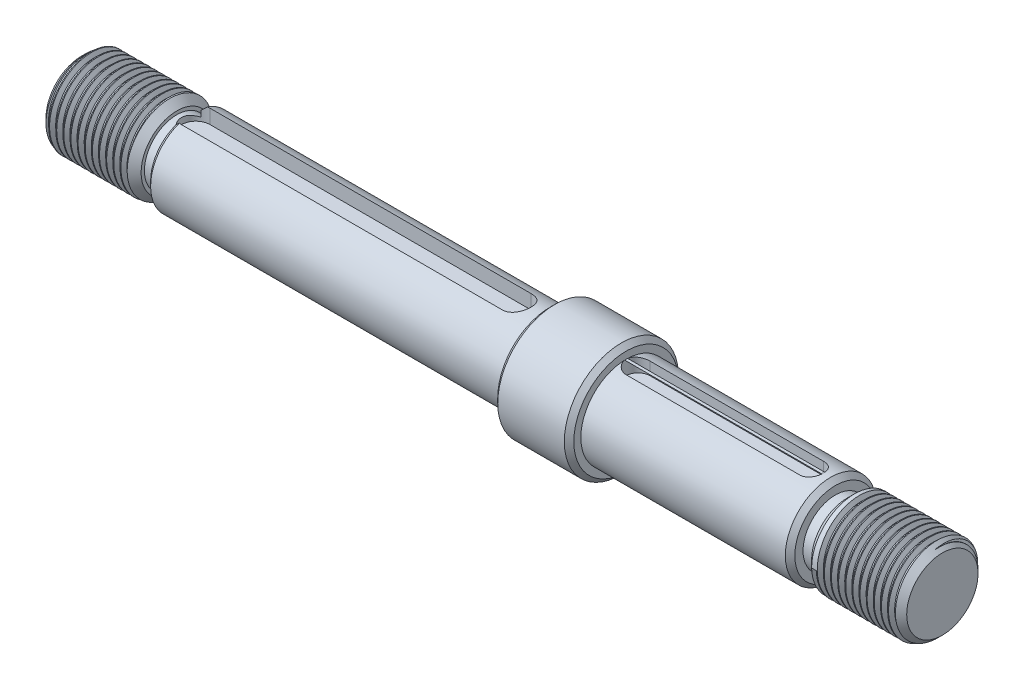
SolidWorks part; units mm, degrees
material "1.0503 (C45)"
ref_plane "前视基准面" through (0, 0, 0) normal (0, 0, 1) x (1, 0, 0)
ref_plane "上视基准面" through (0, 0, 0) normal (0, 1, 0) x (1, 0, 0)
ref_plane "右视基准面" through (0, 0, 0) normal (1, 0, 0) x (0, 0, -1)
sketch "轴轴向刨面" plane through (0, 0, 0) normal (0, 0, 1) x (1, 0, 0)
  line L0 (0, 0) -> (0, 7.5)
  line L3 (23.5, 9) -> (98.5, 9)
  line L4 (98.5, 9) -> (98.5, 11)
  line L5 (99.5, 12) -> (113.5, 12)
  line L6 (114.5, 11) -> (114.5, 9.525)
  line L7 (114.5, 9.525) -> (157.5, 9.525)
  line L8 (181, 7.5) -> (181, 0)
  line L10 (162.5, 9) -> (179.5, 9)
  line L12 (22.5, 6.8) -> (20, 6.8)
  line L13 (20, 6.8) -> (20, 7.5)
  line L14 (1.5, 9) -> (18.5, 9)
  line L16 (158.5, 8.525) -> (158.5, 6.8)
  line L17 (158.5, 6.8) -> (161, 6.8)
  line L18 (161, 6.8) -> (161, 7.5)
  line L19 (22.5, 8) -> (22.5, 6.8)
  line L20 (0, 0) -> (181, 0) construction
  line L21 (0, 0) -> (181, 0)
  line L22 (-25.1387, 0) -> (205.8562, 0) construction
  line L23 (0, 7.5) -> (1.5, 9)
  line L24 (20, 7.5) -> (18.5, 9)
  line L25 (23.5, 9) -> (22.5, 8)
  line L26 (157.5, 9.525) -> (158.5, 8.525)
  line L27 (161, 7.5) -> (162.5, 9)
  line L28 (179.5, 9) -> (181, 7.5)
  line L29 (98.5, 11) -> (99.5, 12)
  line L30 (113.5, 12) -> (114.5, 11)
  point P1 (0, 9)
  point P5 (22.5, 9)
  point P6 (98.5, 12)
  point P7 (158.5, 9.525)
  point P8 (114.5, 12)
  point P10 (161, 9)
  point P11 (181, 9)
  point P15 (20, 9)
  point P19 (0, 0)
  point P20 (0, 0)
  point P25 (0, 0)
  point P38 (0, 0)
  point P39 (161, 7.15)
  dimension "D2" = 20
  dimension "轮毂轴长" = 44
  dimension "40减速机长" = 76
  dimension "轴肩宽" = 16
  dimension "退刀槽宽" = 2.5
  dimension "大端螺纹长度" = 20
  dimension "减速机直径" = 18
  dimension "退刀槽小径" = 13.6
  dimension "轴肩宽直径" = 24
  dimension "轮毂轴直径" = 19.05
revolve "旋转轴" add sketch "轴轴向刨面" angle 360 about L21
ref_plane "9mm键槽面" through (0, 9, 0) normal (0, 1, 0) x (1, 0, 0)
sketch "草图24" plane through (0, 9, 0) normal (0, 1, 0) x (1, 0, 0)
  line L0 (24, 0) -> (91.5, 0) construction
  line L3 (24, 3) -> (91.5, 3)
  line L4 (24, -3) -> (91.5, -3)
  arc A2 (24, 3) -> (24, -3) centre (24, 0) ccw
  arc A3 (91.5, -3) -> (91.5, 3) centre (91.5, 0) ccw
  point P2 (57.75, 0)
  dimension "D2" = 6
extrude "切除-拉伸11" cut sketch "草图24" against normal blind 3.5
ref_plane "9.52mm键槽面" through (0, 9.52, 0) normal (0, 1, 0) x (1, 0, 0)
sketch "草图25" plane through (0, 9.52, 0) normal (0, 1, 0) x (1, 0, 0)
  line L0 (117, 0) -> (153.5, 0) construction
  line L1 (114.5, 0) -> (157.5, 0) construction
  line L2 (117, 2.5) -> (153.5, 2.5)
  line L3 (117, -2.5) -> (153.5, -2.5)
  arc A0 (117, 2.5) -> (117, -2.5) centre (117, 0) ccw
  arc A1 (153.5, -2.5) -> (153.5, 2.5) centre (153.5, 0) ccw
  point P5 (135.25, 0)
  dimension "D1" = 5
extrude "切除-拉伸12" cut sketch "草图25" against normal blind 3
sketch "草图30" plane through (0, 0, 0) normal (-1, 0, 0) x (0, 0, 1)
  circle A0 centre (0, 0) radius 9 construction
  circle A1 centre (0, 0) radius 9
thread "螺纹线1" pitch 1.5 method cut profile "螺纹线轮廓1" start angle 0, offset 1.5, length 18, pitch 1.5, diameter 18
ref_plane "基准面1" through (0, 0, -9) normal (0, -1, 0) x (0, 0, -1)
sketch "螺纹线轮廓1" plane through (0, 0, -9) normal (0, -1, 0) x (0, 0, -1)
  line L0 (0, 0) -> (0, 1.5) construction
  line L11 (0, 0) -> (0, 1.3125)
  line L12 (0, 1.3125) -> (-0.8119, 0.8437)
  line L13 (-0.8119, 0.8437) -> (-0.8119, 0.4687)
  line L15 (-0.8119, 0.4687) -> (0, 0)
  line L17 (-0.8119, 0.6562) -> (0, 0.6562) construction
  point P2 (0, 0)
  dimension "Pitch" = 1.5
  dimension "Profile_Angle" = 60
  dimension "Profile_Land" = 0.375
  dimension "Profile_Height" = 0.8119
thread "螺纹线2" pitch 1.5 method cut profile "螺纹线轮廓2" start angle 0, offset 2, length 18, pitch 1.5, diameter 18
ref_plane "基准面2" through (181.5, 0, 9) normal (0, -1, 0) x (0, 0, 1)
sketch "螺纹线轮廓2" plane through (181.5, 0, 9) normal (0, -1, 0) x (0, 0, 1)
  line L0 (0, 0) -> (0, 1.5) construction
  line L11 (0, 0) -> (0, 1.3125)
  line L12 (0, 1.3125) -> (-0.8119, 0.8437)
  line L13 (-0.8119, 0.8437) -> (-0.8119, 0.4687)
  line L15 (-0.8119, 0.4687) -> (0, 0)
  line L17 (-0.8119, 0.6562) -> (0, 0.6562) construction
  point P2 (0, 0)
  dimension "Pitch" = 1.5
  dimension "Profile_Angle" = 60
  dimension "Profile_Land" = 0.375
  dimension "Profile_Height" = 0.8119
